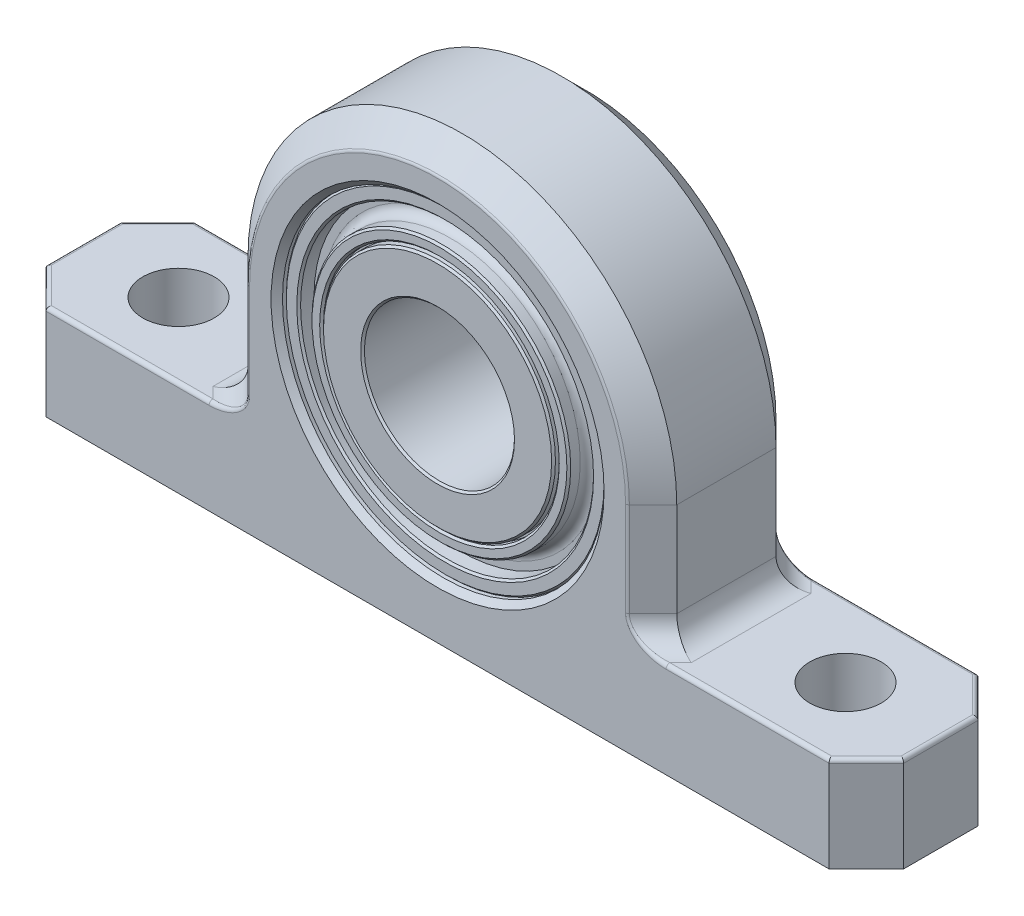
SolidWorks part; units mm, degrees
ref_plane "Front Plane" through (0, 0, 0) normal (0, 0, 1) x (1, 0, 0)
ref_plane "Top Plane" through (0, 0, 0) normal (0, 1, 0) x (1, 0, 0)
ref_plane "Right Plane" through (0, 0, 0) normal (1, 0, 0) x (0, 0, -1)
sketch "Sketch1" plane through (0, 0, 0) normal (0, 0, 1) x (1, 0, 0)
  line L0 (14.2875, 0) -> (14.2875, -7.9375)
  line L1 (14.2875, -7.9375) -> (28.575, -7.9375)
  line L2 (28.575, -7.9375) -> (28.575, -14.2875)
  line L3 (28.575, -14.2875) -> (-28.575, -14.2875)
  line L4 (-28.575, -14.2875) -> (-28.575, -7.9375)
  line L5 (-28.575, -7.9375) -> (-14.2875, -7.9375)
  line L6 (-14.2875, -7.9375) -> (-14.2875, 0)
  circle A0 centre (0, 0) radius 5
  arc A1 (14.2875, 0) -> (-14.2875, 0) centre (0, 0) ccw
  circle A2 centre (0, 0) radius 10.7156
  point P12 (0, 10.7156)
  point P13 (0, 5)
  dimension "shaft dia" = 10
  dimension "D1" = 21.4312
sketch "Sketch2" plane through (0, 0, 0) normal (0, 1, 0) x (1, 0, 0)
  line L0 (0, 4.9609) -> (0, -4.9609) construction
  line L1 (-22.225, 0) -> (22.225, 0) construction
  circle A0 centre (22.225, 0) radius 2.3813
  circle A1 centre (-22.225, 0) radius 2.3813
  dimension "Overall Width" = 9.9219
sketch "Sketch3" plane through (0, 0, 0) normal (0, 0, 1) x (1, 0, 0)
  line L0 (14.2875, 0) -> (14.2875, -7.9375) construction
  line L1 (28.575, -7.9375) -> (28.575, -14.2875) construction
  line L2 (14.2875, -7.9375) -> (28.575, -7.9375) construction
  line L3 (28.575, -14.2875) -> (-28.575, -14.2875) construction
  line L4 (-28.575, -14.2875) -> (-28.575, -7.9375) construction
  line L5 (-28.575, -7.9375) -> (-14.2875, -7.9375) construction
  line L6 (-14.2875, -7.9375) -> (-14.2875, 0) construction
  line L7 (14.2875, 0) -> (14.2875, -7.9375)
  line L8 (28.575, -7.9375) -> (28.575, -14.2875)
  line L9 (14.2875, -7.9375) -> (28.575, -7.9375)
  line L10 (28.575, -14.2875) -> (-28.575, -14.2875)
  line L11 (-28.575, -14.2875) -> (-28.575, -7.9375)
  line L12 (-28.575, -7.9375) -> (-14.2875, -7.9375)
  line L13 (-14.2875, -7.9375) -> (-14.2875, 0)
  arc A0 (14.2875, 0) -> (-14.2875, 0) centre (0, 0) ccw construction
  circle A1 centre (0, 0) radius 10.7156 construction
  arc A2 (14.2875, 0) -> (-14.2875, 0) centre (0, 0) ccw
  circle A3 centre (0, 0) radius 10.7156
extrude "Extrude1" add sketch "Sketch3" along normal up to vertex (4.9609 mm away) and the other way up to vertex (4.9609 mm away) up to point (0, 0, 4.9609) other way up to point (0, 0, -4.9609)
sketch "Sketch4" plane through (0, -7.9375, 0) normal (0, 1, 0) x (1, 0, 0)
  line L0 (-28.575, 4.9609) -> (-28.575, 2.4805)
  line L1 (-28.575, -4.9609) -> (-28.575, 4.9609) construction
  line L2 (-28.575, 2.4805) -> (-26.0945, 4.9609)
  line L3 (-14.2875, 4.9609) -> (-28.575, 4.9609) construction
  line L4 (-26.0945, 4.9609) -> (-28.575, 4.9609)
  line L5 (0, 0) -> (0, 4.9609) construction
  line L6 (0, 0) -> (-22.225, 0) construction
  line L7 (26.0945, 4.9609) -> (28.575, 4.9609)
  line L8 (28.575, 2.4805) -> (26.0945, 4.9609)
  line L9 (28.575, 4.9609) -> (28.575, 2.4805)
  line L10 (28.575, -4.9609) -> (28.575, -2.4805)
  line L11 (28.575, -2.4805) -> (26.0945, -4.9609)
  line L12 (26.0945, -4.9609) -> (28.575, -4.9609)
  line L13 (-26.0945, -4.9609) -> (-28.575, -4.9609)
  line L14 (-28.575, -2.4805) -> (-26.0945, -4.9609)
  line L15 (-28.575, -4.9609) -> (-28.575, -2.4805)
  circle A0 centre (-22.225, 0) radius 2.3813 construction
  circle A1 centre (22.225, 0) radius 2.3813 construction
  circle A2 centre (-22.225, 0) radius 2.3813
  circle A3 centre (22.225, 0) radius 2.3813
  dimension "D1" = 45
  dimension "D2" = 2.4805
extrude "Cut-Extrude1" cut sketch "Sketch4" against normal through all
chamfer "Chamfer3" distance 1.6536 angle 45 6 edges at (-14.2875, -3.9687, -4.9609) (0, 14.2875, -4.9609) (14.2875, -3.9687, -4.9609) (-14.2875, -3.9687, 4.9609) (0, 14.2875, 4.9609) (14.2875, -3.9687, 4.9609)
fillet "Fillet6" radius 1.6536 6 edges at (14.2875, -7.9375, 0) (13.4607, -7.9375, -4.1341) (13.4607, -7.9375, 4.1341) (-13.4607, -7.9375, -4.1341) (-13.4607, -7.9375, 4.1341) (-14.2875, -7.9375, 0)
fillet "Fillet7" radius 0.254 20 edges at (20.5335, -7.9375, -4.9609) (13.3188, -7.4532, -4.9609) (12.6339, -3.1419, -4.9609) (0, 12.6339, -4.9609) (-12.6339, -3.1419, -4.9609) (-13.3188, -7.4532, -4.9609) (20.5335, -7.9375, 4.9609) (13.3188, -7.4532, 4.9609) (12.6339, -3.1419, 4.9609) (0, 12.6339, 4.9609) (-12.6339, -3.1419, 4.9609) (-13.3188, -7.4532, 4.9609) (27.3348, -7.9375, 3.7207) (28.575, -7.9375, 0) (27.3348, -7.9375, -3.7207) (-20.5335, -7.9375, -4.9609) (-27.3348, -7.9375, -3.7207) (-28.575, -7.9375, 0) (-27.3348, -7.9375, 3.7207) (-20.5335, -7.9375, 4.9609)
chamfer "Chamfer4" distance 0.381 angle 45 2 edges at (10.7156, 0, -4.9609) (10.7156, 0, 4.9609)
sketch "Sketch5" plane through (0, 0, 0) normal (1, 0, 0) x (0, 0, -1)
  line L0 (-4.4529, 9.763) -> (-3.4369, 9.763)
  line L1 (0, 10.7156) -> (0, 5) construction
  line L2 (4.4529, 10.7156) -> (4.4529, 9.763)
  line L4 (4.4529, 9.763) -> (3.4369, 9.763)
  line L5 (-3.4369, 9.763) -> (-3.4369, 8.6199)
  line L6 (-3.4369, 8.6199) -> (-4.8339, 8.6199)
  line L7 (-4.3259, 7.7308) -> (-4.3259, 7.8578)
  line L8 (-4.9609, 5) -> (4.9609, 5)
  line L9 (-4.3259, 7.7308) -> (-4.9609, 7.7308)
  line L10 (-4.4529, 10.7156) -> (4.4529, 10.7156)
  line L11 (3.4369, 9.763) -> (3.4369, 8.6199)
  line L12 (-4.9609, 7.7308) -> (-4.9609, 5)
  line L13 (-4.4529, 10.7156) -> (-4.4529, 9.763)
  line L15 (-4.3259, 7.8578) -> (-4.8339, 7.8578)
  line L16 (-4.8339, 7.8578) -> (-4.8339, 8.6199)
  line L17 (0, 10.7156) -> (0, 14.2875) construction
  line L18 (0, 14.2875) -> (0, 0) construction
  line L19 (3.4369, 8.6199) -> (4.8339, 8.6199)
  line L20 (4.8339, 7.8578) -> (4.8339, 8.6199)
  line L21 (4.3259, 7.8578) -> (4.8339, 7.8578)
  line L22 (4.3259, 7.7308) -> (4.3259, 7.8578)
  line L23 (4.3259, 7.7308) -> (4.9609, 7.7308)
  line L24 (4.9609, 7.7308) -> (4.9609, 5)
  line L27 (3.3073, 14.2875) -> (-3.3073, 14.2875) construction
  point P9 (0, 7.8578)
  dimension "D1" = 5.7156
  dimension "D2" = 0.9526
  dimension "D3" = 1.1431
  dimension "D6" = 1.016
  dimension "D5" = 0.635
  dimension "D7" = 0.127
  dimension "D8" = 0.127
  dimension "D9" = 0.508
revolve "Revolve1" add sketch "Sketch5" angle 360 about L0
chamfer "Chamfer5" distance 0.127 angle 45 12 edges at (-7.7308, 0, 4.9609) (-5, 0, 4.9609) (-8.6199, 0, 4.8339) (-7.8578, 0, 4.8339) (-10.7156, 0, 4.4529) (-9.763, 0, 4.4529) (-5, 0, -4.9609) (-7.7308, 0, -4.9609) (-7.8578, 0, -4.8339) (-8.6199, 0, -4.8339) (-9.763, 0, -4.4529) (-10.7156, 0, -4.4529)
fillet "Fillet8" radius 0.635 2 edges at (-8.6199, 0, 3.4369) (-8.6199, 0, -3.4369)
equation "\"D1@Sketch1\"=\"I@Sketch1\"*.75"
equation "\"D2@Sketch4\" = \"Overall Width@Sketch2\" / 4"
equation "\"D1@Chamfer3\" = \"Overall Width@Sketch2\" / 6"
equation "\"D1@Fillet6\"=\"D1@Chamfer3\""
equation "\"D2@Sketch5\"=\"D1@Sketch5\"/6"
equation "\"D3@Sketch5\"=\"D2@Sketch5\"*1.2"
